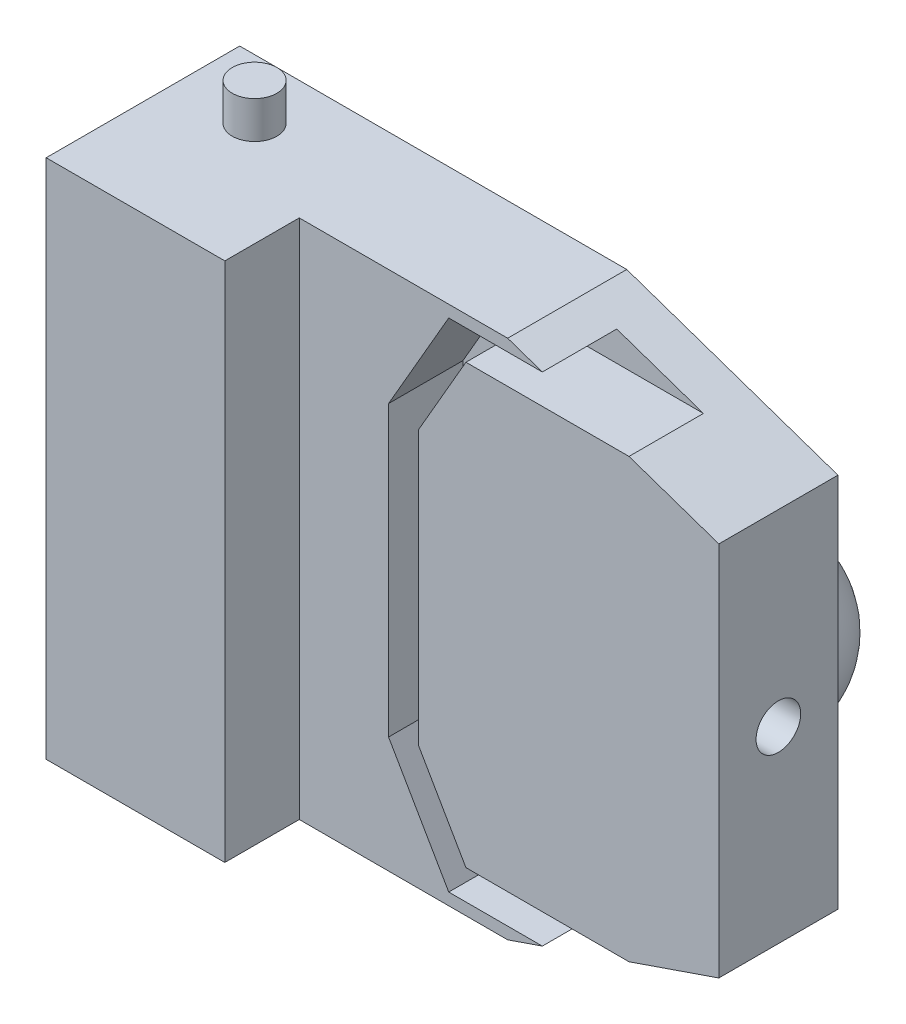
SolidWorks part; units mm, degrees
ref_plane "Front Plane" through (0, 0, 0) normal (0, 0, 1) x (1, 0, 0)
ref_plane "Top Plane" through (0, 0, 0) normal (0, 1, 0) x (1, 0, 0)
ref_plane "Right Plane" through (0, 0, 0) normal (1, 0, 0) x (0, 0, -1)
sketch "Sketch1" plane through (0, 0, 0) normal (0, 0, 1) x (1, 0, 0)
  line L8 (0, 0) -> (-260, 0)
  line L9 (-260, 0) -> (-260, -350)
  line L10 (-260, -350) -> (0, -350)
  line L11 (0, 0) -> (141.8631, -48.7326)
  line L12 (141.8631, -48.7326) -> (141.8631, -301.2674)
  line L13 (141.8631, -301.2674) -> (0, -350)
  point P6 (141.8631, -175)
  point P7 (-260, -175)
  dimension "D2" = 260
  dimension "D3" = 150
  dimension "D1" = 350
  dimension "D4" = 252.5348
extrude "Boss-Extrude1" add sketch "Sketch1" along normal blind 80
sketch "Sketch2" plane through (0, -350, 0) normal (0, -1, 0) x (1, 0, 0)
  line L0 (-260, 40) -> (0, 40) construction
  line L1 (-260, 80) -> (-260, 0) construction
  line L3 (-210, 80) -> (-210, 0) construction
  line L4 (-260, 80) -> (0, 80) construction
  line L5 (-260, 0) -> (0, 0) construction
  line L6 (0, 80) -> (0, 0) construction
  circle A0 centre (-210, 40) radius 15
  dimension "D2" = 30
  dimension "D1" = 50
  dimension "D3" = 50
extrude "Boss-Extrude2" add sketch "Sketch2" along normal blind 25 from surface starting at face at (-130, -350, 40)
extrude "Boss-Extrude3" add sketch "Sketch2<2>" against normal blind 25 from surface starting at face at (-130, 0, 40)
sketch "Sketch2<2>" plane through (0, -350, 0) normal (0, -1, 0) x (1, 0, 0) same geometry as "Sketch2"
sketch "Sketch3" plane through (0, 0, 0) normal (0, 0, -1) x (-1, 0, 0)
  line L0 (-141.8631, -175) -> (260, -175) construction
  line L1 (260, 0) -> (260, -350) construction
  line L2 (-11.8631, -175) -> (-131.8631, -175)
  line L3 (-141.8631, -301.2674) -> (-141.8631, -48.7326) construction
  arc A1 (-11.8631, -175) -> (-131.8631, -175) centre (-71.8631, -175) ccw
  dimension "D1" = 60
  dimension "D2" = 70
sketch "Sketch4" plane through (141.8631, 0, 0) normal (1, 0, 0) x (0, 0, -1)
  line L0 (0, -301.2674) -> (0, -48.7326) construction
  line L1 (-80, -48.7326) -> (0, -48.7326) construction
  circle A0 centre (-40, -175) radius 15
  point P5 (0, -175)
  point P9 (-40, -48.7326)
  dimension "D1" = 30
extrude "Cut-Extrude1" cut sketch "Sketch4" against normal blind 30
sketch "Sketch5" plane through (0, 0, 80) normal (0, 0, 1) x (1, 0, 0)
  line L0 (23.2884, -342) -> (-39.5855, -342)
  line L1 (0, -350) -> (141.8631, -301.2674) construction
  line L2 (-260, -350) -> (0, -350) construction
  line L3 (-260, -175) -> (141.8631, -175) construction
  line L4 (-39.5855, -342) -> (-80, -272)
  line L5 (-260, 0) -> (-260, -350) construction
  line L6 (141.8631, -301.2674) -> (141.8631, -48.7326) construction
  line L7 (-39.5855, -8) -> (-80, -78)
  line L8 (23.2884, -8) -> (-39.5855, -8)
  line L9 (-80, -272) -> (-80, -78)
  line L10 (81.5094, -322) -> (-28.0385, -322)
  line L11 (-28.0385, -322) -> (-60, -266.641)
  line L12 (-60, -266.641) -> (-60, -83.359)
  line L13 (-60, -83.359) -> (-28.0385, -28)
  line L14 (-28.0385, -28) -> (81.5094, -28)
  line L15 (141.8631, -48.7326) -> (0, 0) construction
  line L16 (23.2884, -342) -> (81.5094, -322)
  line L17 (23.2884, -8) -> (81.5094, -28)
  dimension "D1" = 8
  dimension "D3" = 120
  dimension "D4" = 70
  dimension "D2" = 180
  dimension "D5" = 20
  dimension "D6" = 20
  dimension "D7" = 20
  dimension "D8" = 20
  dimension "D9" = 20
extrude "Cut-Extrude3" cut sketch "Sketch5" against normal blind 50 contours L11 L12 L13 L14 L17 L8 L7 L9 L4 L0 L16 L10
revolve "Revolve1" add sketch "Sketch3" angle 180 about L0
sketch "Sketch6" plane through (0, 0, 80) normal (0, 0, 1) x (1, 0, 0)
  line L0 (0, 0) -> (-260, 0) construction
  line L1 (-140, 0) -> (-260, 0)
  line L2 (-140, 0) -> (-140, -350)
  line L3 (-140, -350) -> (-260, -350)
  line L4 (-260, 0) -> (-260, -350)
  dimension "D1" = 120
extrude "Boss-Extrude4" add sketch "Sketch6" along normal blind 50
sketch "Sketch7" plane through (0, 0, 0) normal (0, 0, -1) x (-1, 0, 0)
  line L0 (-141.8631, -175) -> (260, -175) construction
  line L1 (-141.8631, -301.2674) -> (-141.8631, -48.7326) construction
  line L2 (260, 0) -> (260, -350) construction
  line L3 (59.07, 0) -> (59.07, -350) construction
  line L4 (260, -350) -> (0, -350) construction
  dimension "D1" = 200.93
ref_point "Point2"
